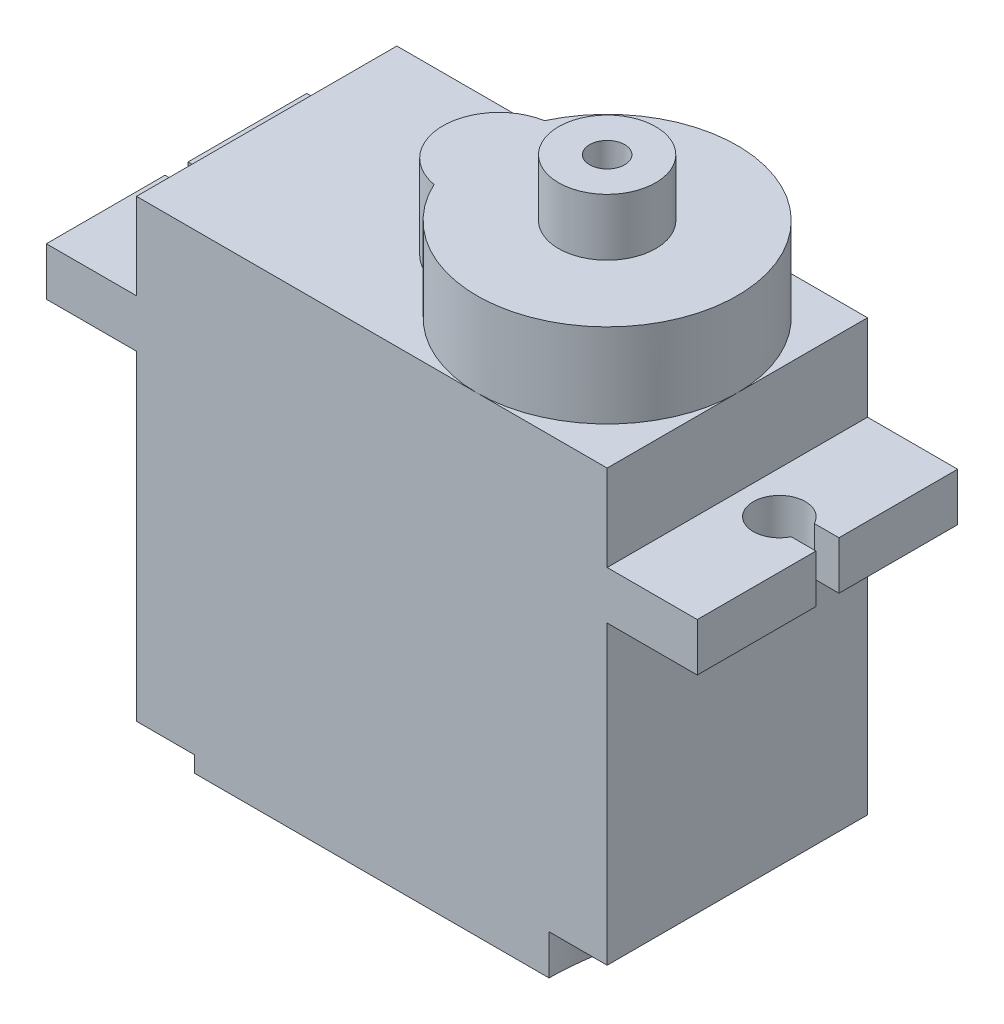
SolidWorks part; units mm, degrees
ref_plane "Alzado" through (0, 0, 0) normal (0, 0, 1) x (1, 0, 0)
ref_plane "Planta" through (0, 0, 0) normal (0, 1, 0) x (1, 0, 0)
ref_plane "Vista lateral" through (0, 0, 0) normal (1, 0, 0) x (0, 0, -1)
sketch "Croquis1" plane through (0, 0, 0) normal (0, 0, 1) x (1, 0, 0)
  line L0 (0, 11.75) -> (0, -11.75) construction
  line L4 (-11.75, -11.75) -> (-11.75, 11.75)
  line L5 (-11.75, 11.75) -> (11.75, 11.75)
  line L6 (-11.75, -11.75) -> (11.75, -11.75)
  line L7 (-16.25, 5.05) -> (-11.75, 5.05)
  line L8 (-16.25, 5.05) -> (-16.25, 7.45)
  line L9 (-16.25, 7.45) -> (-11.75, 7.45)
  line L10 (-11.75, 5.05) -> (-11.75, 7.45)
  line L11 (-16.25, 5.05) -> (-11.75, 7.45) construction
  line L12 (-16.25, 7.45) -> (-11.75, 5.05) construction
  line L14 (11.75, -11.75) -> (11.75, 11.75)
  line L16 (16.25, 7.45) -> (11.75, 7.45)
  line L17 (11.75, 5.05) -> (11.75, 7.45)
  line L18 (16.25, 5.05) -> (11.75, 5.05)
  line L19 (16.25, 5.05) -> (16.25, 7.45)
  point P0 (0, 0)
  point P2 (-11.75, 0)
  point P6 (-14, 6.25)
  dimension "D1" = 23.5
  dimension "D2" = 2.4
  dimension "D3" = 23.5
  dimension "D4" = 4.5
  dimension "D5" = 4.3
extrude "Saliente-Extruir1" add sketch "Croquis1" along normal mid plane 13 contours L9 L8 L7 L4 | L6 L14 L5 L4 | L18 L19 L16 L14 region at (0, 0, 0) region at (-14, 6.25, 0) region at (14, 6.25, 0)
sketch "Croquis2" plane through (0, 11.75, 0) normal (0, 1, 0) x (1, 0, 0)
  line L0 (-11.75, 6.5) -> (11.75, 6.5) construction
  line L1 (-11.75, -6.5) -> (11.75, -6.5) construction
  line L2 (11.75, -6.5) -> (11.75, 6.5) construction
  line L3 (-0.15, 0) -> (-2.95, 0) construction
  arc A0 (-0.6361, -2.7575) -> (-0.6361, 2.7575) centre (5.25, 0) ccw
  arc A1 (-0.6361, 2.7575) -> (-0.6361, -2.7575) centre (-0.15, 0) ccw
  dimension "D2" = 5.6
  dimension "D1" = 14.7
extrude "Saliente-Extruir2" add sketch "Croquis2" along normal blind 4.2
sketch "Croquis3" plane through (0, 7.45, 0) normal (0, 1, 0) x (1, 0, 0)
  line L0 (0, -6.5) -> (0, 6.5) construction
  line L1 (-11.75, -6.5) -> (5.25, -6.5) construction
  line L2 (-11.75, 6.5) -> (5.25, 6.5) construction
  line L3 (16.25, 0.575) -> (15.0159, 0.575)
  line L4 (16.25, -6.5) -> (16.25, 6.5) construction
  line L5 (16.25, -0.575) -> (15.0159, -0.575)
  line L6 (16.25, 0.575) -> (16.25, -0.575)
  line L7 (-16.25, 0.575) -> (-15.0159, 0.575)
  line L8 (-16.25, 0.575) -> (-16.25, -0.575)
  line L9 (-16.25, -0.575) -> (-15.0159, -0.575)
  arc A1 (15.0159, 0.575) -> (15.0159, -0.575) centre (13.85, 0) ccw
  arc A2 (-15.0159, 0.575) -> (-15.0159, -0.575) centre (-13.85, 0) cw
  point P16 (16.25, 0)
  point P18 (16.25, 0)
  dimension "D2" = 2.6
  dimension "D1" = 1.15
  dimension "D3" = 2.4
extrude "Cortar-Extruir1" cut sketch "Croquis3" against normal up to next
sketch "Croquis4" plane through (0, -11.75, 0) normal (0, -1, 0) x (1, 0, 0)
  line L0 (0, 6.5) -> (0, -6.5) construction
  line L1 (-11.75, 0) -> (11.75, 0) construction
  line L2 (-11.75, 3.6) -> (-11.75, 6.5)
  line L3 (-11.75, 6.5) -> (-8.85, 6.5)
  line L4 (-11.75, -6.5) -> (11.75, -6.5)
  line L5 (11.75, -6.5) -> (11.75, 6.5)
  line L6 (11.75, 6.5) -> (-11.75, 6.5)
  line L7 (-11.75, 6.5) -> (-11.75, -6.5)
  line L8 (-11.75, -6.5) -> (11.75, -6.5)
  line L9 (11.75, -6.5) -> (11.75, 6.5)
  line L10 (11.75, 6.5) -> (-11.75, 6.5)
  line L11 (-11.75, 6.5) -> (-11.75, -6.5)
  line L12 (-11.75, -3.6) -> (-11.75, -6.5)
  line L13 (-11.75, -6.5) -> (-8.85, -6.5)
  line L14 (11.75, 3.6) -> (11.75, 6.5)
  line L15 (11.75, 6.5) -> (8.85, 6.5)
  line L16 (11.75, -3.6) -> (11.75, -6.5)
  line L17 (11.75, -6.5) -> (8.85, -6.5)
  line L18 (8.85, 6.5) -> (8.85, -6.5)
  line L19 (10.25, -1.875) -> (11.75, -1.875)
  line L20 (10.25, -1.875) -> (10.25, 1.875)
  line L21 (10.25, 1.875) -> (11.75, 1.875)
  line L22 (11.75, -1.875) -> (11.75, 1.875)
  line L23 (10.25, -1.875) -> (11.75, 1.875) construction
  line L24 (10.25, 1.875) -> (11.75, -1.875) construction
  arc A0 (-8.85, 6.5) -> (-11.75, 3.6) centre (-11.75, 6.5) cw
  arc A1 (-8.85, -6.5) -> (-11.75, -3.6) centre (-11.75, -6.5) ccw
  arc A2 (8.85, 6.5) -> (11.75, 3.6) centre (11.75, 6.5) ccw
  arc A3 (8.85, -6.5) -> (11.75, -3.6) centre (11.75, -6.5) cw
  point P17 (11, 0)
  dimension "D2" = 2.9
  dimension "D3" = 3.75
  dimension "D4" = 1.5
  dimension "D1" = 0
extrude "Cortar-Extruir3" cut sketch "Croquis4" against normal blind 0.8 contours A0 L16 L4 | L17 A1 L11 region at (-10.5192, -11.75, 5.2692) region at (-10.5192, -11.75, -5.2692)
extrude "Cortar-Extruir4" cut sketch "Croquis4<5>" against normal blind 2 contours L16 A2 L9 | L21 L20 L19 A3 | A3 L17 region at (10.5192, -11.75, 5.2692) region at (10.5192, -11.75, -5.2692) region at (11, -11.75, 0)
sketch "Croquis4<5>" plane through (0, -11.75, 0) normal (0, -1, 0) x (1, 0, 0) same geometry as "Croquis4"
sketch "Croquis6" plane through (0, 0, -6.5) normal (0, 0, -1) x (-1, 0, 0)
  line L0 (-11.75, -9.75) -> (-8.85, -11.75)
  line L1 (-8.85, -11.75) -> (-11.75, -11.75)
  line L2 (-11.75, -11.75) -> (-11.75, -9.75)
extrude "Cortar-Extruir5" cut sketch "Croquis6" against normal through all
sketch "Croquis7" plane through (0, 15.95, 0) normal (0, 1, 0) x (1, 0, 0)
  circle A0 centre (5.25, 0) radius 2.425
  circle A1 centre (5.25, 0) radius 0.875
  dimension "D1" = 4.85
  dimension "D2" = 1.55
extrude "Saliente-Extruir4" add sketch "Croquis7" along normal blind 2.85
